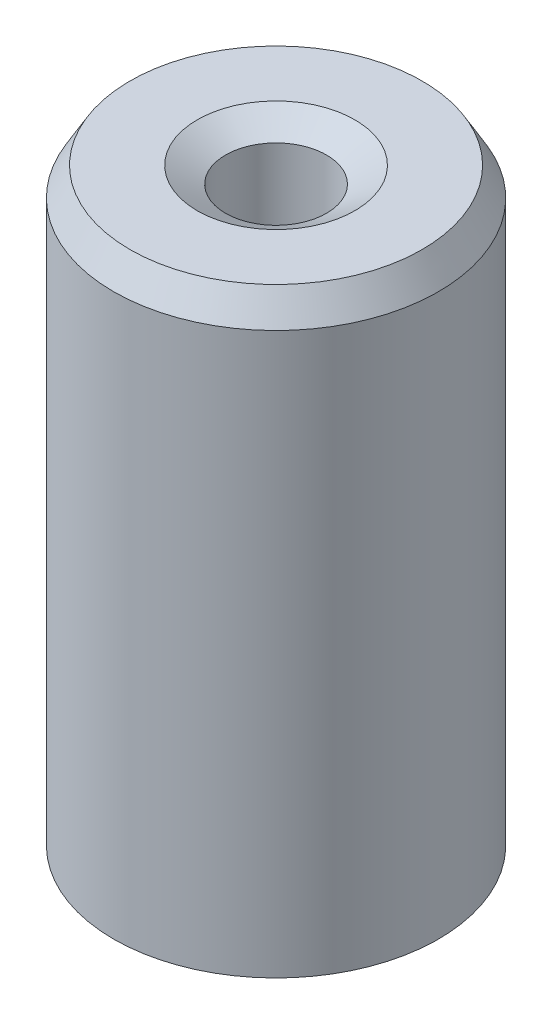
SolidWorks part; units mm, degrees
ref_plane "Front Plane" through (0, 0, 0) normal (0, 0, 1) x (1, 0, 0)
ref_plane "Top Plane" through (0, 0, 0) normal (0, 1, 0) x (1, 0, 0)
ref_plane "Right Plane" through (0, 0, 0) normal (1, 0, 0) x (0, 0, -1)
sketch "Sketch1" plane through (0, 0, 0) normal (0, 1, 0) x (1, 0, 0)
  circle A0 centre (0, 0) radius 7.5
  dimension "SLEEVE_OD" = 15
extrude "Boss-Extrude1" add sketch "Sketch1" along normal blind 27.9559
sketch "Sketch2" plane through (0, 0, 0) normal (0, 1, 0) x (1, 0, 0)
  circle A0 centre (0, 0) radius 2.3319
  dimension "BORE_D" = 4.6638
extrude "Cut-Extrude1" cut sketch "Sketch2" along normal through all
chamfer "Chamfer1" distance 1.3072 angle 30 4 edges at (0, 27.9559, 2.3319) (0, 0, 2.3319) (0, 0, 7.5) (0, 27.9559, 7.5) first distance on face at (0, 27.9559, 2.3319) first distance on face at (0, 0, 2.3319) first distance on face at (0, 27.9559, 7.5)
